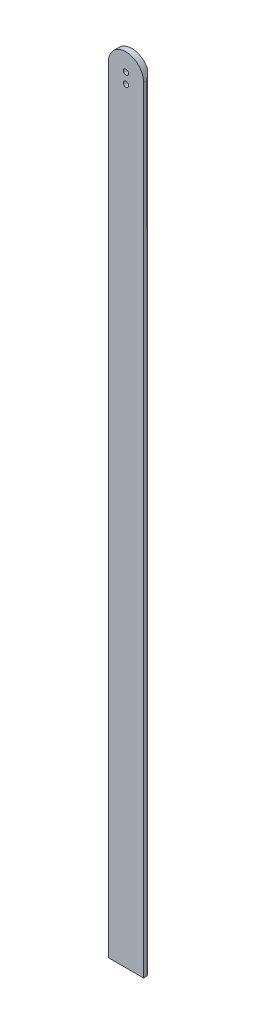
SolidWorks part; units mm, degrees
material "6061 Alloy"
ref_plane "Front Plane" through (0, 0, 0) normal (0, 0, 1) x (1, 0, 0)
ref_plane "Top Plane" through (0, 0, 0) normal (0, 1, 0) x (1, 0, 0)
ref_plane "Right Plane" through (0, 0, 0) normal (1, 0, 0) x (0, 0, -1)
sketch "Sketch2" plane through (0, 0, 0) normal (0, 1, 0) x (1, 0, 0)
  line L0 (0, 0) -> (19.05, 0)
  line L1 (0, 0) -> (0, 19.05)
  line L2 (4.7625, 3.175) -> (17.4625, 3.175)
  line L3 (3.175, 4.7625) -> (3.175, 17.4625)
  line L4 (0, 19.05) -> (1.5875, 19.05)
  line L5 (19.05, 1.5875) -> (19.05, 0)
  line L6 (3.175, 3.175) -> (3.175, 19.05) construction
  line L7 (3.175, 3.175) -> (19.05, 3.175) construction
  arc A0 (3.175, 17.4625) -> (1.5875, 19.05) centre (1.5875, 17.4625) ccw
  arc A1 (3.175, 4.7625) -> (4.7625, 3.175) centre (4.7625, 4.7625) ccw
  arc A2 (17.4625, 3.175) -> (19.05, 1.5875) centre (17.4625, 1.5875) cw
  dimension "D2" = 1.5875
  dimension "D1" = 3.175
extrude "Boss-Extrude1" add sketch "Sketch2" along normal blind 431.8
sketch "Sketch4" plane through (3.175, 0, 0) normal (1, 0, 0) x (0, 0, -1)
  line L0 (19.05, 431.8) -> (19.05, 406.4)
  line L1 (19.05, 431.8) -> (19.05, 0) construction
  line L2 (19.05, 406.4) -> (3.175, 406.4)
  line L3 (3.175, 431.8) -> (3.175, 0) construction
  line L4 (3.175, 406.4) -> (3.175, 431.8)
  line L5 (3.175, 431.8) -> (19.05, 431.8)
extrude "Cut-Extrude1" cut sketch "Sketch4" against normal blind 6.35
sketch "Sketch5" plane through (3.175, 0, 0) normal (-1, 0, 0) x (0, 0, 1)
  line L8 (-4.7625, 406.4) -> (-3.175, 406.4)
  line L9 (-3.175, 406.4) -> (-3.175, 431.8)
  line L10 (-3.175, 431.8) -> (-4.7625, 431.8)
  line L11 (-4.7625, 431.8) -> (-4.7625, 406.4)
  line L12 (-4.7625, 406.4) -> (-3.175, 406.4)
  line L13 (-3.175, 406.4) -> (-3.175, 431.8)
  line L14 (-3.175, 431.8) -> (-4.7625, 431.8)
  line L15 (-4.7625, 431.8) -> (-4.7625, 406.4)
  dimension "D1" = 0
extrude "Cut-Extrude2" cut sketch "Sketch5" against normal blind 6.35
sketch "Sketch6" plane through (3.175, 0, 0) normal (1, 0, 0) x (0, 0, -1)
  line L0 (19.05, 0) -> (3.175, 0) construction
  line L1 (11.1125, 0) -> (11.1125, 15.875) construction
  line L2 (19.05, 406.4) -> (3.175, 406.4) construction
  line L3 (11.1125, 406.4) -> (11.1125, 390.525) construction
  line L4 (11.1125, 15.875) -> (11.1125, 203.2) construction
  line L5 (11.1125, 203.2) -> (11.1125, 390.525) construction
  circle A1 centre (11.1125, 109.5375) radius 1.4224
  circle A2 centre (11.1125, 203.2) radius 1.4224
  circle A3 centre (11.1125, 296.8625) radius 1.4224
  circle A5 centre (11.1125, 11.1125) radius 1.4224
  circle A6 centre (11.1125, 395.2875) radius 1.4224
  point P12 (11.1125, 203.2)
  point P13 (11.1125, 296.8625)
  point P15 (11.1125, 109.5375)
  dimension "D2" = 2.8448
  dimension "D3" = 2.8448
  dimension "D4" = 2.8448
  dimension "D6" = 2.8448
  dimension "D7" = 2.8448
extrude "Cut-Extrude3" cut sketch "Sketch6" against normal blind 5.08
sketch "Sketch7" plane through (0, 431.8, 0) normal (0, 1, 0) x (1, 0, 0)
  line L8 (17.4625, 3.175) -> (0, 3.175)
  line L9 (0, 3.175) -> (0, 0)
  line L10 (0, 0) -> (19.05, 0)
  line L11 (19.05, 0) -> (19.05, 1.5875)
  line L12 (17.4625, 3.175) -> (0, 3.175)
  line L13 (0, 3.175) -> (0, 0)
  line L14 (0, 0) -> (19.05, 0)
  line L15 (19.05, 0) -> (19.05, 1.5875)
  arc A2 (19.05, 1.5875) -> (17.4625, 3.175) centre (17.4625, 1.5875) ccw
  arc A3 (19.05, 1.5875) -> (17.4625, 3.175) centre (17.4625, 1.5875) ccw
  dimension "D1" = 0
extrude "Cut-Extrude4" cut sketch "Sketch7" against normal blind 2.54
sketch "Sketch8" plane through (0, 0, -3.175) normal (0, 0, -1) x (-1, 0, 0)
  line L0 (0, 429.26) -> (0, 419.735) construction
  line L1 (0, 429.26) -> (0, 406.4) construction
  line L2 (0, 419.735) -> (-9.525, 419.735) construction
  line L3 (-9.525, 419.735) -> (-9.525, 414.02) construction
  circle A0 centre (-9.525, 419.735) radius 1.4224
  circle A1 centre (-9.525, 414.02) radius 1.4224
  dimension "D1" = 2.8448
  dimension "D3" = 2.8448
  dimension "D2" = 5.715
extrude "Cut-Extrude5" cut sketch "Sketch8" against normal blind 5.08
ref_plane "Plane1" through (0, 0, 2.54) normal (0, 0, 1) x (1, 0, 0)
sketch "Sketch10" plane through (0, 0, -3.175) normal (0, 0, -1) x (-1, 0, 0)
  line L0 (-9.525, 419.735) -> (-19.05, 429.26) construction
  line L6 (0, 419.735) -> (0, 429.26)
  line L7 (0, 429.26) -> (-19.05, 429.26)
  line L8 (-19.05, 419.735) -> (-19.05, 429.26)
  line L10 (0, 429.26) -> (-9.525, 419.735) construction
  arc A2 (0, 419.735) -> (-19.05, 419.735) centre (-9.525, 419.735) ccw
  line M3 (0, 429.26) -> (-17.4625, 429.26)
  line M4 (-17.4625, 429.26) -> (-17.4625, 0)
  line M8 (0, 406.4) -> (0, 429.26)
extrude "Cut-Extrude7" cut sketch "Sketch10" against normal blind 5.08 contours M8 M3 | M4 | M4 region at (2.1276, 427.1324, -3.175) region at (15.5776, 428.0522, -3.175) region at (18.3487, 426.1569, -3.175)
